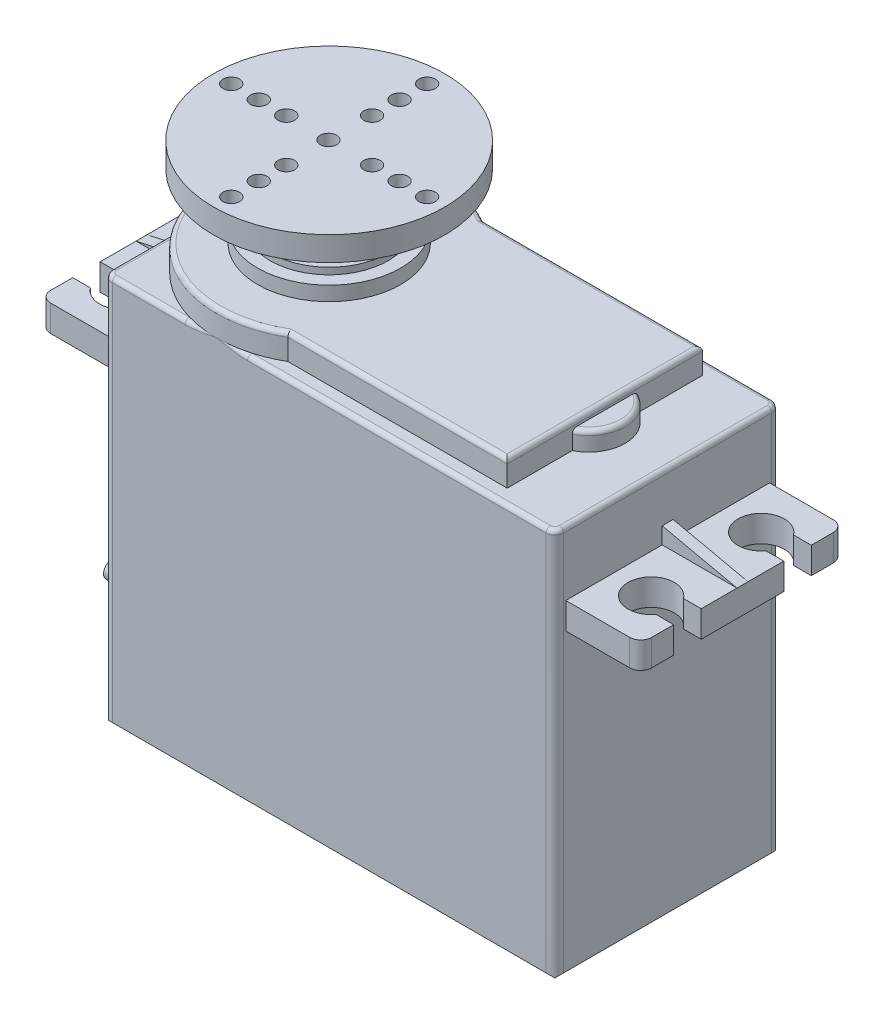
SolidWorks part; units mm, degrees
ref_plane "Front Plane" through (0, 0, 0) normal (0, 0, 1) x (1, 0, 0)
ref_plane "Top Plane" through (0, 0, 0) normal (0, 1, 0) x (1, 0, 0)
ref_plane "Right Plane" through (0, 0, 0) normal (1, 0, 0) x (0, 0, -1)
sketch "Sketch1" plane through (0, 0, 0) normal (0, 1, 0) x (1, 0, 0)
  line L1 (-20.5, -10.25) -> (20.5, -10.25)
  line L2 (-20.5, -10.25) -> (-20.5, 10.25)
  line L3 (-20.5, 10.25) -> (20.5, 10.25)
  line L4 (20.5, -10.25) -> (20.5, 10.25)
  line L5 (-20.5, -10.25) -> (20.5, 10.25) construction
  line L6 (-20.5, 10.25) -> (20.5, -10.25) construction
  point P0 (0, 0)
  dimension "D1" = 41
  dimension "D2" = 20.5
extrude "Boss-Extrude1" add sketch "Sketch1" along normal blind 37
sketch "Sketch2" plane through (0, 37, 0) normal (0, 1, 0) x (1, 0, 0)
  line L0 (-20.5, 10.25) -> (-20.5, -10.25) construction
  line L1 (20.5, -10.25) -> (20.5, 10.25) construction
  line L2 (-5.122, -8.875) -> (14.8, -8.875)
  line L4 (-5.122, 8.875) -> (14.8, 8.875)
  line L5 (14.8, -8.875) -> (14.8, -2.9672)
  line L9 (14.8, 2.9672) -> (14.8, 8.875)
  arc A0 (-5.122, 8.875) -> (-5.122, -8.875) centre (-10.25, 0) ccw
  arc A1 (14.8, -2.9672) -> (14.8, 2.9672) centre (13.3208, 0) ccw
  point P5 (4.4919, 0)
  dimension "D1" = 10.25
  dimension "D2" = 17.75
  dimension "D3" = 5.7
extrude "Boss-Extrude2" add sketch "Sketch2" along normal blind 2.3
sketch "Sketch3" plane through (0, 39.3, 0) normal (0, 1, 0) x (1, 0, 0)
  circle A0 centre (-10.25, 0) radius 6.5
  dimension "D1" = 13
extrude "Boss-Extrude3" add sketch "Sketch3" along normal blind 1.3
sketch "Sketch4" plane through (0, 40.6, 0) normal (0, 1, 0) x (1, 0, 0)
  circle A0 centre (-10.25, 0) radius 5.35
  dimension "D1" = 10.7
extrude "Boss-Extrude4" add sketch "Sketch4" along normal blind 0.6
sketch "Sketch5" plane through (0, 39.3, 0) normal (0, 1, 0) x (1, 0, 0)
  line L0 (14.8, 2.9672) -> (14.8, -2.9672)
  arc A0 (14.8, -2.9672) -> (14.8, 2.9672) centre (13.3208, 0) ccw construction
  arc A1 (14.8, -2.9672) -> (14.8, 2.9672) centre (13.3208, 0) ccw
extrude "Cut-Extrude1" cut sketch "Sketch5" against normal blind 0.6
sketch "Sketch6" plane through (0, 41.2, 0) normal (0, 1, 0) x (1, 0, 0)
  circle A0 centre (-10.25, 0) radius 3
  dimension "D1" = 6
extrude "Boss-Extrude5" add sketch "Sketch6" along normal blind 4
chamfer "Chamfer1" distance 2 angle 45 4 edges at (-20.5, 0, 0) (0, 0, -10.25) (20.5, 0, 0) (0, 0, 10.25)
fillet "Fillet2" radius 0.8 4 edges at (-20.5, 19.5, -10.25) (-20.5, 19.5, 10.25) (20.5, 19.5, -10.25) (20.5, 19.5, 10.25)
sketch "Sketch7" plane through (-20.5, 0, 0) normal (-1, 0, 0) x (0, 0, 1)
  line L1 (-9.25, 31.2) -> (9.25, 31.2)
  line L2 (-9.25, 31.2) -> (-9.25, 28.8)
  line L3 (-9.25, 28.8) -> (9.25, 28.8)
  line L4 (9.25, 31.2) -> (9.25, 28.8)
  line L6 (-9.45, 37) -> (0, 37) construction
  line L9 (-10.25, 37) -> (-10.25, 2) construction
  dimension "D1" = 5.8
  dimension "D2" = 2.4
  dimension "D3" = 18.5
  dimension "D4" = 1
extrude "Boss-Extrude6" add sketch "Sketch7" along normal blind 6.8
sketch "Sketch9" plane through (0, 31.2, 0) normal (0, 1, 0) x (1, 0, 0)
  line L0 (-27.3, -9.25) -> (-27.3, 9.25) construction
  line L3 (-25.6875, 6.25) -> (-27.3, 6.25)
  line L4 (-21.6, 3.75) -> (-22.3125, 3.75)
  line L5 (-21.6, 3.75) -> (-21.6, 6.25)
  line L6 (-21.6, 6.25) -> (-22.3125, 6.25)
  line L7 (-27.3, 3.75) -> (-27.3, 6.25)
  line L8 (-21.6, 3.75) -> (-24, 5) construction
  line L9 (-21.6, 6.25) -> (-24, 5) construction
  line L10 (-21.6, -6.25) -> (-27.3, -6.25)
  line L11 (-21.6, -6.25) -> (-21.6, -3.75)
  line L12 (-21.6, -3.75) -> (-27.3, -3.75)
  line L13 (-27.3, -6.25) -> (-27.3, -3.75)
  line L14 (-21.6, -6.25) -> (-24, -5) construction
  line L15 (-21.6, -3.75) -> (-24, -5) construction
  line L18 (-25.6875, 3.75) -> (-27.3, 3.75)
  arc A0 (-25.6875, 3.75) -> (-25.6875, 6.25) centre (-24, 5) ccw
  arc A1 (-25.6875, -6.25) -> (-25.6875, -3.75) centre (-24, -5) ccw
  line M4 (-27.3, 9.25) -> (-27.3, -9.25)
  dimension "D1" = 4.2
  dimension "D2" = 4.2
  dimension "D3" = 3.3
  dimension "D4" = 10
  dimension "D5" = 5
  dimension "D6" = 2.5
  dimension "D7" = 2.5
  dimension "D8" = 3.3
extrude "Cut-Extrude2" cut sketch "Sketch9" against normal blind 6.8 contours A0 L3 L18 M4 | L12 A1 | L10 A1 | L10 A1 L12 M4 region at (-24.5093, 31.2, -5) region at (-24.6644, 31.2, 5) region at (-24, 31.2, 3.4033) region at (-24, 31.2, 6.5967)
fillet "Fillet1" radius 1 2 edges at (-27.3, 30, 9.25) (-27.3, 30, -9.25)
sketch "Sketch10" plane through (0, 31.2, 0) normal (0, 1, 0) x (1, 0, 0)
  line L0 (-20.5, -9.25) -> (-20.5, 9.25) construction
  line L1 (-27.3, -0.5) -> (-20.5, -0.5)
  line L2 (-27.3, -0.5) -> (-27.3, 0.5)
  line L3 (-27.3, 0.5) -> (-20.5, 0.5)
  line L4 (-20.5, -0.5) -> (-20.5, 0.5)
  line L5 (-27.3, -0.5) -> (-20.5, 0.5) construction
  line L6 (-27.3, 0.5) -> (-20.5, -0.5) construction
  line L7 (-27.3, -3.75) -> (-27.3, 3.75) construction
  point P0 (-23.9, 0)
  dimension "D1" = 1
extrude "Boss-Extrude7" add sketch "Sketch10" along normal blind 1.5
sketch "Sketch11" plane through (0, 0, 0.5) normal (0, 0, 1) x (1, 0, 0)
  line L0 (-27.3, 31.2) -> (-20.5, 32.7)
  line L1 (-20.5, 32.7) -> (-27.3, 32.7)
  line L2 (-27.3, 32.7) -> (-27.3, 31.2)
extrude "Cut-Extrude3" cut sketch "Sketch11" against normal blind 1.5
ref_plane "Plane1" through (0, 0, 0) normal (-1, 0, 0) x (0, 0, 1)
mirror "Mirror2" about plane through (0, 0, 0) normal (-1, 0, 0) of "Cut-Extrude3", "Boss-Extrude7", "Fillet1", "Cut-Extrude2", "Boss-Extrude6"
sketch "Sketch12" plane through (0, 45.2, 0) normal (0, 1, 0) x (1, 0, 0)
  circle A0 centre (-10.25, 0) radius 1.25
  dimension "D1" = 2.5
extrude "Cut-Extrude4" cut sketch "Sketch12" against normal blind 4
fillet "Fillet5" radius 0.4 5 edges at (16.6363, 38.7, 0) (14.8, 39.3, 0) (4.839, 39.3, -8.875) (-20.5, 39.3, 0) (4.839, 39.3, 8.875)
fillet "Fillet7" radius 0.4 11 edges at (20.2657, 37, 10.0157) (4.725, 37, 10.25) (-14.975, 37, 10.25) (-20.2657, 37, 10.0157) (-20.5, 37, 4.725) (-20.5, 37, -4.725) (-20.2657, 37, -10.0157) (-14.975, 37, -10.25) (4.725, 37, -10.25) (20.2657, 37, -10.0157) (20.5, 37, 0)
sketch "Sketch13" plane through (-20.5, 0, 0) normal (-1, 0, 0) x (0, 0, 1)
  line L0 (8.25, 0) -> (-8.25, 0) construction
  line L1 (-3.5, 3.2) -> (3.5, 3.2)
  line L2 (-3.5, 3.2) -> (-3.5, 7.4)
  line L3 (-3.5, 7.4) -> (3.5, 7.4)
  line L4 (3.5, 3.2) -> (3.5, 7.4)
  line L5 (-3.5, 3.2) -> (3.5, 7.4) construction
  line L6 (-3.5, 7.4) -> (3.5, 3.2) construction
  point P0 (0, 5.3)
  dimension "D1" = 7
  dimension "D2" = 4.2
  dimension "D3" = 3.2
extrude "Boss-Extrude8" add sketch "Sketch13" along normal blind 1
sketch "Sketch14" plane through (-21.5, 0, 0) normal (-1, 0, 0) x (0, 0, 1)
  line L9 (3.15, 3.55) -> (3.15, 7.05)
  line L10 (3.15, 7.05) -> (-3.15, 7.05)
  line L11 (-3.15, 7.05) -> (-3.15, 3.55)
  line L12 (-3.15, 3.55) -> (3.15, 3.55)
  line L13 (3.15, 3.55) -> (3.15, 7.05)
  line L14 (3.15, 7.05) -> (-3.15, 7.05)
  line L15 (-3.15, 7.05) -> (-3.15, 3.55)
  line L16 (-3.15, 3.55) -> (3.15, 3.55)
  dimension "D1" = 0.35
extrude "Boss-Extrude9" add sketch "Sketch14" along normal blind 4 draft 5 contours L14 L15 L16 L13
sketch "Sketch15" plane through (-25.5, 0, 0) normal (-1, 0, 0) x (0, 0, 1)
  line L0 (-2.8, 3.9) -> (2.8, 3.9) construction
  circle A0 centre (-1.5, 5.3) radius 0.75
  circle A1 centre (0, 5.3) radius 0.75
  circle A2 centre (1.5, 5.3) radius 0.75
  dimension "D1" = 1.5
  dimension "D2" = 1.5
  dimension "D3" = 1.5
  dimension "D4" = 1.4
extrude "Boss-Extrude12" add sketch "Sketch15" along normal blind 3 separate body contours A0 | A1 | A2 region at (-25.5, 5.3, -1.5) region at (-25.5, 5.3, 1.5) region at (-25.5, 5.3, 0)
sketch "Sketch16" plane through (0, 45.2, 0) normal (0, 1, 0) x (1, 0, 0)
  circle A0 centre (-10.25, 0) radius 10.5
  dimension "D1" = 21
extrude "Boss-Extrude13" add sketch "Sketch16" along normal blind 2.2
sketch "Sketch17" plane through (0, 47.4, 0) normal (0, 1, 0) x (1, 0, 0)
  circle A0 centre (-19.1465, 0) radius 0.75
  circle A1 centre (-16.6465, 0) radius 0.75
  circle A2 centre (-14.1465, 0) radius 0.75
  circle A3 centre (-10.25, 3.8965) radius 0.75
  circle A4 centre (-10.25, 6.3965) radius 0.75
  circle A5 centre (-10.25, 8.8965) radius 0.75
  circle A6 centre (-6.3535, 0) radius 0.75
  circle A7 centre (-3.8535, 0) radius 0.75
  circle A8 centre (-1.3535, 0) radius 0.75
  circle A9 centre (-10.25, -3.8965) radius 0.75
  circle A10 centre (-10.25, -6.3965) radius 0.75
  circle A11 centre (-10.25, -8.8965) radius 0.75
  point P3 (-10.25, 0)
  point P29 (-10.25, 0)
  dimension "D1" = 3
  dimension "D2" = 1.5
  dimension "D3" = 4
extrude "Cut-Extrude5" cut sketch "Sketch17" against normal up to next (2.2 mm away)
sketch "Sketch18" plane through (0, 47.4, 0) normal (0, 1, 0) x (1, 0, 0)
  circle A0 centre (-10.3158, 0) radius 0.75
extrude "Cut-Extrude6" cut sketch "Sketch18" against normal blind 10
